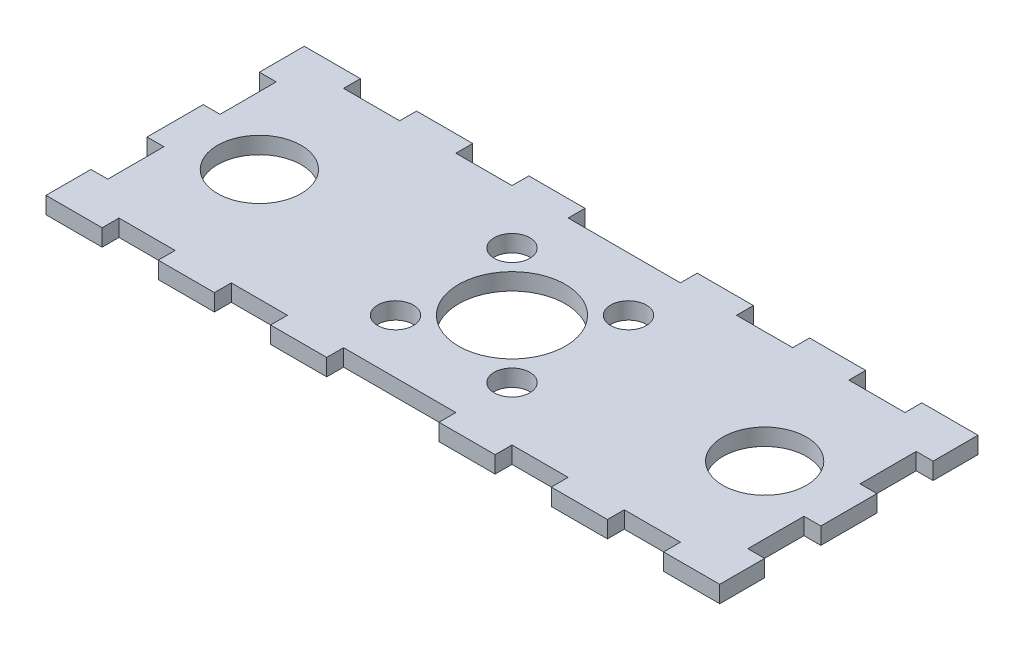
SolidWorks part; units mm, degrees
material "PC High Viscosity"
ref_plane "Front Plane" through (0, 0, 0) normal (0, 0, 1) x (1, 0, 0)
ref_plane "Top Plane" through (0, 0, 0) normal (0, 1, 0) x (1, 0, 0)
ref_plane "Right Plane" through (0, 0, 0) normal (1, 0, 0) x (0, 0, -1)
sketch "Sketch1" plane through (0, 0, 0) normal (0, 1, 0) x (1, 0, 0)
  line L1 (-60, -20) -> (60, -20)
  line L2 (-60, -20) -> (-60, 20)
  line L3 (-60, 20) -> (60, 20)
  line L4 (60, -20) -> (60, 20)
  line L5 (-60, -20) -> (60, 20) construction
  line L6 (-60, 20) -> (60, -20) construction
  point P0 (0, 0)
  dimension "D1" = 120
  dimension "D2" = 40
extrude "Boss-Extrude1" add sketch "Sketch1" along normal blind 3
sketch "Sketch2" plane through (0, 3, 0) normal (0, 1, 0) x (1, 0, 0)
  line L0 (0, -20) -> (0, 20) construction
  line L1 (-60, -20) -> (60, -20) construction
  line L2 (60, 20) -> (-60, 20) construction
  line L4 (-10.375, 10.375) -> (10.375, 10.375) construction
  line L5 (-10.375, 10.375) -> (-10.375, -10.375) construction
  line L6 (-10.375, -10.375) -> (10.375, -10.375) construction
  line L7 (10.375, 10.375) -> (10.375, -10.375) construction
  line L8 (-10.375, 10.375) -> (10.375, -10.375) construction
  line L9 (-10.375, -10.375) -> (10.375, 10.375) construction
  circle A0 centre (45, 0) radius 7.45
  circle A1 centre (-45, 0) radius 7.45
  circle A2 centre (0, 0) radius 9.525
  circle A3 centre (10.375, 10.375) radius 3.175
  circle A4 centre (10.375, -10.375) radius 3.175
  circle A5 centre (-10.375, -10.375) radius 3.175
  circle A6 centre (-10.375, 10.375) radius 3.175
  dimension "D1" = 14.9
  dimension "D2" = 90
  dimension "D3" = 19.05
  dimension "D5" = 6.35
  dimension "D4" = 20.75
extrude "Cut-Extrude1" cut sketch "Sketch2" against normal through all
sketch "Sketch4" plane through (0, 3, 0) normal (0, 1, 0) x (1, 0, 0)
  line L0 (0, 20) -> (0, -20) construction
  line L1 (60, 20) -> (-60, 20) construction
  line L2 (-60, -20) -> (60, -20) construction
  line L3 (-60, 0) -> (60, 0) construction
  line L4 (-60, 20) -> (-60, -20) construction
  line L5 (60, -20) -> (60, 20) construction
  line L6 (20, 20) -> (30, 20) construction
  line L7 (10, 20) -> (20, 20)
  line L8 (10, 20) -> (10, 23)
  line L9 (10, 23) -> (20, 23)
  line L10 (20, 20) -> (20, 23)
  line L11 (30, 20) -> (40, 20)
  line L12 (30, 20) -> (30, 23)
  line L13 (30, 23) -> (40, 23)
  line L14 (40, 20) -> (40, 23)
  line L15 (40, 20) -> (50, 20) construction
  line L16 (60, 20) -> (50, 20)
  line L17 (60, 20) -> (60, 23)
  line L18 (60, 23) -> (50, 23)
  line L19 (50, 20) -> (50, 23)
  line L20 (-50, 20) -> (-50, 23)
  line L21 (-60, 23) -> (-50, 23)
  line L22 (-60, 20) -> (-60, 23)
  line L23 (-60, 20) -> (-50, 20)
  line L24 (-40, 20) -> (-40, 23)
  line L25 (-30, 23) -> (-40, 23)
  line L26 (-30, 20) -> (-30, 23)
  line L27 (-30, 20) -> (-40, 20)
  line L28 (-20, 20) -> (-20, 23)
  line L29 (-10, 23) -> (-20, 23)
  line L30 (-10, 20) -> (-10, 23)
  line L31 (-10, 20) -> (-20, 20)
  line L32 (40, -20) -> (50, -20) construction
  line L33 (20, -20) -> (30, -20) construction
  line L34 (-10, -20) -> (-20, -20)
  line L35 (-10, -20) -> (-10, -23)
  line L36 (-10, -23) -> (-20, -23)
  line L37 (-20, -20) -> (-20, -23)
  line L38 (-30, -20) -> (-40, -20)
  line L39 (-30, -20) -> (-30, -23)
  line L40 (-30, -23) -> (-40, -23)
  line L41 (-40, -20) -> (-40, -23)
  line L42 (-60, -20) -> (-50, -20)
  line L43 (-60, -20) -> (-60, -23)
  line L44 (-60, -23) -> (-50, -23)
  line L45 (-50, -20) -> (-50, -23)
  line L46 (50, -20) -> (50, -23)
  line L47 (60, -23) -> (50, -23)
  line L48 (60, -20) -> (60, -23)
  line L49 (60, -20) -> (50, -20)
  line L50 (40, -20) -> (40, -23)
  line L51 (30, -23) -> (40, -23)
  line L52 (30, -20) -> (30, -23)
  line L53 (30, -20) -> (40, -20)
  line L54 (20, -20) -> (20, -23)
  line L55 (10, -23) -> (20, -23)
  line L56 (10, -20) -> (10, -23)
  line L57 (10, -20) -> (20, -20)
  dimension "D1" = 10
  dimension "D2" = 3
extrude "Boss-Extrude2" add sketch "Sketch4" against normal up to surface (3 mm away) up to face at (-10.375, 0, -7.2)
sketch "Sketch5" plane through (0, 3, 0) normal (0, 1, 0) x (1, 0, 0)
  line L0 (60, -23) -> (60, 23) construction
  line L1 (60, 5) -> (57, 5)
  line L2 (60, 5) -> (60, 15)
  line L3 (60, 15) -> (57, 15)
  line L4 (57, 5) -> (57, 15)
  line L5 (60, 0) -> (0, 0) construction
  line L6 (57, -5) -> (57, -15)
  line L7 (60, -15) -> (57, -15)
  line L8 (60, -5) -> (60, -15)
  line L9 (60, -5) -> (57, -5)
  line L10 (60, -5) -> (60, 5) construction
  dimension "D1" = 3
  dimension "D2" = 10
extrude "Cut-Extrude2" cut sketch "Sketch5" against normal through all
mirror "Mirror1" about plane through (0, 0, 0) normal (1, 0, 0) of "Cut-Extrude2"
equation "\"pulley_pitch_diam\"= 12.73mm"
equation "\"pulley_total_width\"= 16mm"
equation "\"pulley_total_diam\"= 16mm"
equation "\"belt_width\"= 6mm"
equation "\"material_thickness\"= 3mm"
equation "\"shaft_diam\"= 8mm"
equation "\"bearing_od\"= 22mm"
equation "\"bearing_thickness\"= 7mm"
equation "\"D1@Boss-Extrude1\"=\"material_thickness\""
equation "\"D2@Sketch4\"=\"material_thickness\""
equation "\"D1@Sketch5\"=\"material_thickness\""
